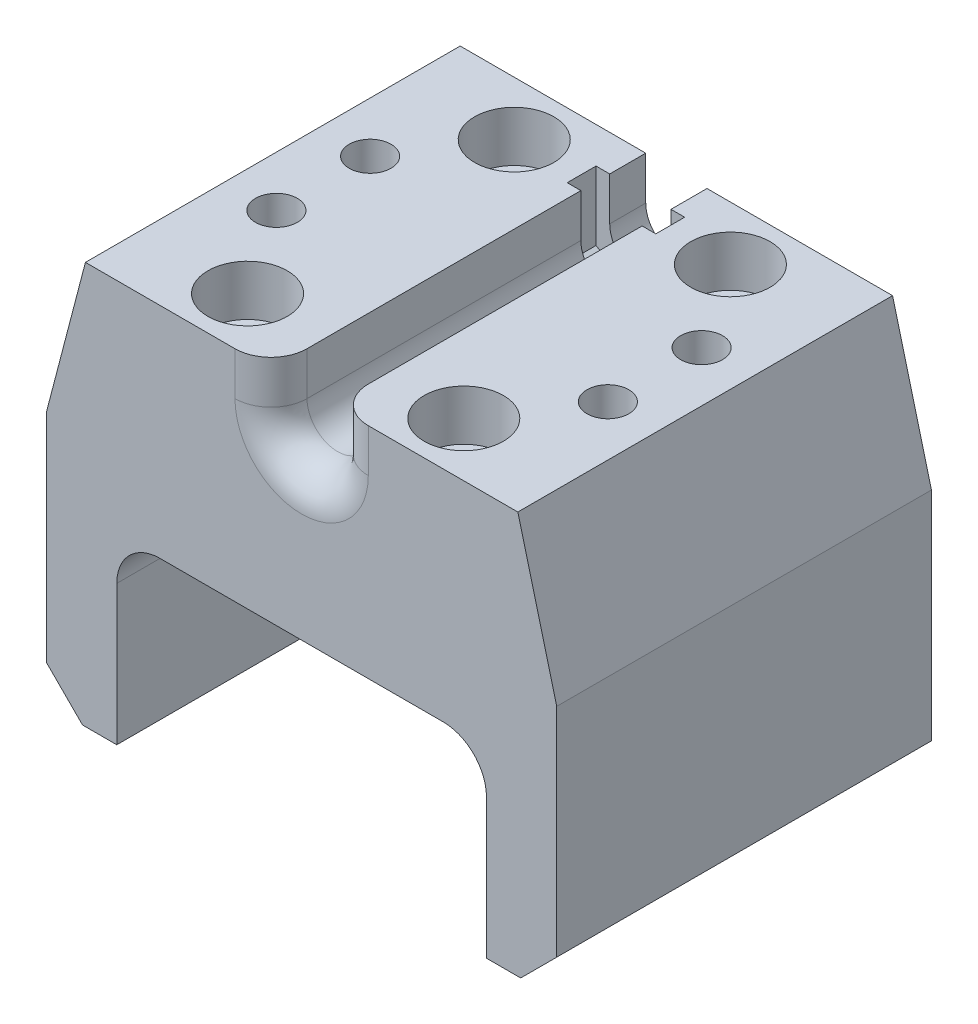
SolidWorks part; units mm, degrees
material "PET"
ref_plane "Front Plane" through (0, 0, 0) normal (0, 0, 1) x (1, 0, 0)
ref_plane "Top Plane" through (0, 0, 0) normal (0, 1, 0) x (1, 0, 0)
ref_plane "Right Plane" through (0, 0, 0) normal (1, 0, 0) x (0, 0, -1)
sketch "Sketch1" plane through (0, 0, 0) normal (0, 0, 1) x (1, 0, 0)
  line L0 (0, 19.0297) -> (0, -2.5925) construction
  line L1 (-12.9623, 0) -> (13.1829, 0) construction
  line L2 (35.4, 6) -> (-35.4, 6)
  line L3 (-35.4, 6) -> (-35.4, -49.8)
  line L4 (-35.4, -49.8) -> (-25.65, -49.8)
  line L5 (-25.65, -49.8) -> (-25.65, -24.4)
  line L6 (-25.65, -24.4) -> (25.65, -24.4)
  line L7 (35.4, -49.8) -> (25.65, -49.8)
  line L8 (25.65, -49.8) -> (25.65, -24.4)
  line L9 (35.4, 6) -> (35.4, -49.8)
  circle A0 centre (0, 0) radius 3.75 construction
  point P16 (0, -24.4)
  point P17 (0, 6)
  dimension "D1" = 7.5
  dimension "D2" = 6
  dimension "D5" = 51.3
  dimension "D6" = 24.4
  dimension "D3" = 70.8
  dimension "D4" = 25.4
extrude "Boss-Extrude1" add sketch "Sketch1" along normal mid plane 52
sketch "Sketch9" plane through (0, 0, 26) normal (0, 0, 1) x (1, 0, 0)
  line L0 (0, 0) -> (0, -24.4) construction
  line L1 (-25.65, -24.4) -> (25.65, -24.4) construction
  line L2 (-30, 6) -> (-35.4, -14.65)
  line L3 (35.4, 6) -> (-35.4, 6) construction
  line L4 (-35.4, 6) -> (-35.4, -49.8) construction
  line L5 (-35.4, -14.65) -> (-35.4, 6)
  line L6 (-35.4, 6) -> (-30, 6)
  line L7 (-25.65, -24.4) -> (-35.4, -24.4) construction
  line L8 (-35.4, -24.4) -> (-35.4, -14.65) construction
  line L9 (35.4, 6) -> (30, 6)
  line L10 (35.4, -14.65) -> (35.4, 6)
  line L11 (30, 6) -> (35.4, -14.65)
  dimension "D1" = 30
extrude "Cut-Extrude8" cut sketch "Sketch9" against normal through all
fillet "Fillet1" radius 6 2 edges at (25.65, -24.4, 0) (-25.65, -24.4, 0)
sketch "Sketch2" plane through (0, 6, 0) normal (0, 1, 0) x (1, 0, 0)
  line L0 (0, 35.9356) -> (0, 6.1551) construction
  line L1 (-23, 6.5) -> (-23, -6.5) construction
  line L3 (30, 26) -> (-30, 26) construction
  line L7 (0, 0) -> (-35.4, 0) construction
  line L8 (-35.4, 26) -> (-35.4, -26) construction
  circle A2 centre (-23, 6.5) radius 2.9
  circle A3 centre (-23, -6.5) radius 2.9
  circle A4 centre (-15, 18.5) radius 3.05
  circle A5 centre (23, -6.5) radius 2.9
  circle A6 centre (23, 6.5) radius 2.9
  circle A7 centre (15, 18.5) radius 3.05
  circle A8 centre (15, -18.5) radius 3.05
  circle A9 centre (-15, -18.5) radius 3.05
  dimension "D2" = 5.8
  dimension "D3" = 12
  dimension "D4" = 6.1
  dimension "D5" = 13
  dimension "D6" = 23
  dimension "D9" = 7.5
  dimension "D10" = 15
extrude "Cut-Extrude1" cut sketch "Sketch2" against normal blind 29
sketch "Sketch3" plane through (0, 6, 0) normal (0, 1, 0) x (1, 0, 0)
  circle A0 centre (-15, 18.5) radius 5.5
  circle A1 centre (15, 18.5) radius 5.5
  circle A2 centre (-15, -18.5) radius 5.5
  circle A3 centre (15, -18.5) radius 5.5
  dimension "D1" = 11
extrude "Cut-Extrude2" cut sketch "Sketch3" against normal blind 7
chamfer "Chamfer2" distance 5 angle 45 2 edges at (-35.4, -49.8, 0) (35.4, -49.8, 0)
sketch "Sketch10" plane through (0, 0, -26) normal (0, 0, -1) x (-1, 0, 0)
  line L1 (-4.25, 0) -> (-4.25, 11.4915)
  line L2 (-4.25, 11.4915) -> (4.25, 11.4915)
  line L3 (4.25, 11.4915) -> (4.25, 0)
  arc A0 (-4.25, 0) -> (4.25, 0) centre (0, 0) ccw
  dimension "D1" = 8.5
extrude "Cut-Extrude9" cut sketch "Sketch10" against normal through all
sketch "Sketch11" plane through (0, 0, -26) normal (0, 0, -1) x (-1, 0, 0)
  line L0 (-6.15, 3.5507) -> (-6.15, 9.9104)
  line L1 (-6.15, 3.5507) -> (-6.15, -3.5507)
  line L2 (-6.15, -3.5507) -> (0, -7.1014)
  line L3 (0, -7.1014) -> (6.15, -3.5507)
  line L4 (6.15, -3.5507) -> (6.15, 3.5507)
  line L5 (6.15, 3.5507) -> (0, 7.1014) construction
  line L6 (0, 7.1014) -> (-6.15, 3.5507) construction
  line L7 (-6.15, 9.9104) -> (6.15, 9.9104)
  line L8 (6.15, 9.9104) -> (6.15, 3.5507)
  circle A0 centre (0, 0) radius 6.15 construction
  dimension "D1" = 12.3
extrude "Cut-Extrude10" cut sketch "Sketch11" against normal blind 4 from offset 5 offset against normal yes
fillet "Fillet2" radius 5 3 edges at (4.25, 3, 26) (-4.25, 3, 26) (0, -4.25, 26)
sketch "Sketch12" plane through (0, -23, 0) normal (0, 1, 0) x (1, 0, 0)
  circle A0 centre (-15, 18.5) radius 3.05 construction
  circle A1 centre (15, 18.5) radius 3.05 construction
  circle A2 centre (15, -18.5) radius 3.05 construction
  circle A3 centre (-15, -18.5) radius 3.05 construction
  circle A4 centre (-15, 18.5) radius 3.05
  circle A5 centre (15, 18.5) radius 3.05
  circle A6 centre (15, -18.5) radius 3.05
  circle A7 centre (-15, -18.5) radius 3.05
extrude "Cut-Extrude11" cut sketch "Sketch12" against normal blind 4
fillet "Fillet3" radius 2 4 edges at (-25.9, -23, -6.5) (-25.9, -23, 6.5) (25.9, -23, -6.5) (25.9, -23, 6.5)
equation "\"M5_tap\"=4.2mm       ' Below you can do mesurements as follows: cm, mm, ft, in, m, "
equation "\"M5_clearence\"=5.5mm"
equation "\"M6_tap\"=5mm"
equation "\"M6_clearence\"=6.6mm"
equation "\"work_area_width\"=1100mm"
equation "\"work_area_depth\"=900mm"
equation "\"steel_base_width\"=3in "
equation "\"steel_base_height\"=2in"
equation "\"steel_base_wall_thickness\"=0.125in"
equation "\"steel_base_radius\"=6mm"
equation "\"steel_sides_width\"=3in     'this tube is rotated so flip width/height"
equation "\"steel_sides_height\"=2in    'this tube is rotated so flip width/height"
equation "\"steel_sides_wall_thickness\"=0.125in"
equation "\"steel_sides_radius\"=6mm"
equation "\"steel_gantry_width\"=4in    'this tube is rotated so flip width/height"
equation "\"steel_gantry_height\"=3in    'this tube is rotated so flip width/height"
equation "\"steel_gantry_wall_thickness\"=0.125in"
equation "\"steel_gantry_radius\"=6mm"
equation "\"steel_rollers_width\"=3in"
equation "\"steel_rollers_height\"=2in    'keep as low as possible as this increases how big plastic parts are"
equation "\"steel_rollers_wall_thickness\"=0.125in"
equation "\"steel_rollers_radius\"=6mm"
equation "\"steel_zbox_width\"=4in     'if the gantry height (rotated) is too thick, a wider zbox is necessary"
equation "\"steel_zbox_height\"=2in     'hole patteren changes as the zbox and gantry height (rotated) changes."
equation "\"steel_zbox_wall_thickness\"=0.125in"
equation "\"steel_zbox_radius\"=6mm"
equation "\"alu_zangle_width\"=4in     'check that it doesn't interfer with the gantry"
equation "\"alu_zangle_height\"=4in"
equation "\"alu_zangle_wall_thickness\"=0.375in   'check that it doesn't interfer with the gantry"
equation "\"D3@Sketch1\"=\"steel_sides_height\" + 20"
equation "\"D6@Sketch1\"=\"steel_rollers_height\" /2 -1"
equation "\"D4@Sketch1\"=\"steel_sides_width\"/3"
